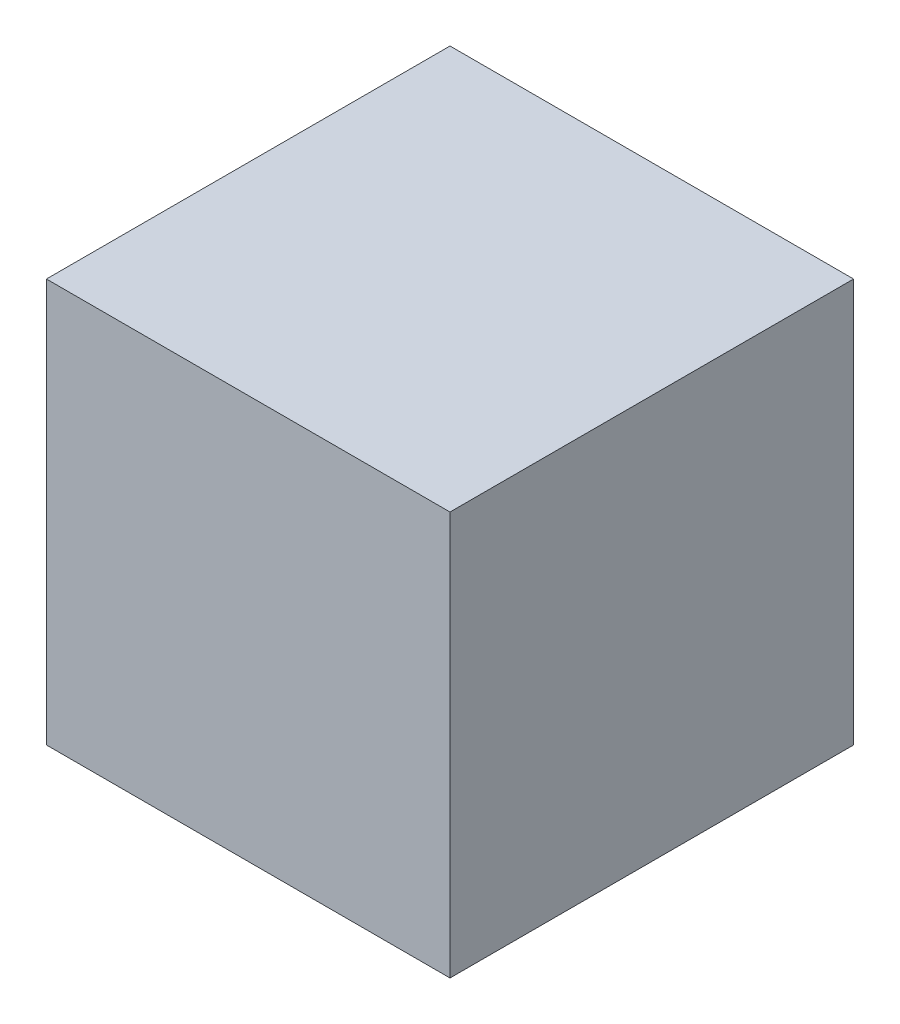
SolidWorks part; units mm, degrees
material "Oak"
ref_plane "Front Plane" through (0, 0, 0) normal (0, 0, 1) x (1, 0, 0)
ref_plane "Top Plane" through (0, 0, 0) normal (0, 1, 0) x (1, 0, 0)
ref_plane "Right Plane" through (0, 0, 0) normal (1, 0, 0) x (0, 0, -1)
sketch "Sketch1" plane through (0, 0, 0) normal (0, 1, 0) x (1, 0, 0)
  line L1 (0, 0) -> (127, 0)
  line L2 (0, 0) -> (0, 127)
  line L3 (0, 127) -> (127, 127)
  line L4 (127, 0) -> (127, 127)
  dimension "D1" = 127
extrude "Boss-Extrude1" add sketch "Sketch1" along normal blind 127
